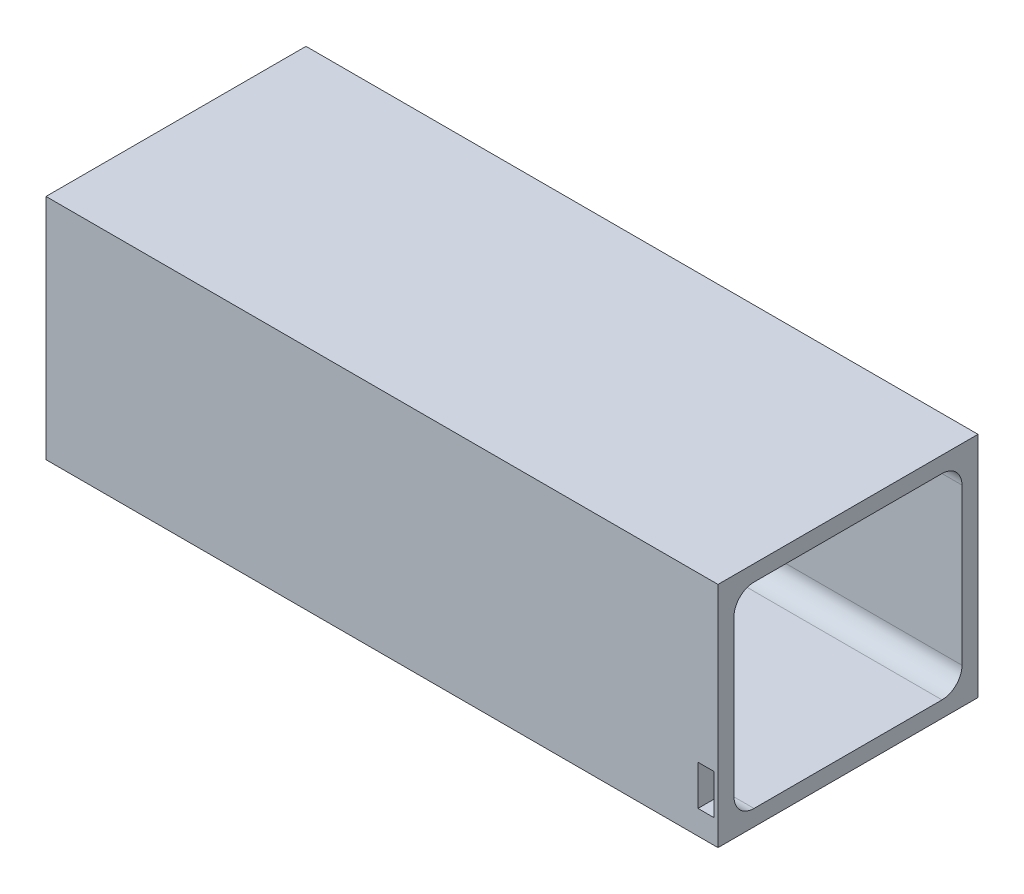
SolidWorks part; units mm, degrees
material "PET"
ref_plane "Спереди" through (0, 0, 0) normal (0, 0, 1) x (1, 0, 0)
ref_plane "Сверху" through (0, 0, 0) normal (0, 1, 0) x (1, 0, 0)
ref_plane "Справа" through (0, 0, 0) normal (1, 0, 0) x (0, 0, -1)
sketch "Эскиз1" plane through (0, 0, 0) normal (1, 0, 0) x (0, 0, -1)
  line L1 (23.5, -24.5) -> (-23.5, -24.5)
  line L2 (28.5, -19.5) -> (28.5, 19.5)
  line L3 (23.5, 24.5) -> (-23.5, 24.5)
  line L4 (-28.5, -19.5) -> (-28.5, 19.5)
  line L5 (28.5, -24.5) -> (-28.5, 24.5) construction
  line L6 (28.5, 24.5) -> (-28.5, -24.5) construction
  line L7 (32.5, -28.5) -> (-32.5, -28.5)
  line L8 (32.5, -28.5) -> (32.5, 28.5)
  line L9 (32.5, 28.5) -> (-32.5, 28.5)
  line L10 (-32.5, -28.5) -> (-32.5, 28.5)
  line L11 (32.5, -28.5) -> (-32.5, 28.5) construction
  line L12 (32.5, 28.5) -> (-32.5, -28.5) construction
  arc A0 (-23.5, -24.5) -> (-28.5, -19.5) centre (-23.5, -19.5) cw
  arc A1 (23.5, -24.5) -> (28.5, -19.5) centre (23.5, -19.5) ccw
  arc A2 (28.5, 19.5) -> (23.5, 24.5) centre (23.5, 19.5) ccw
  arc A3 (-23.5, 24.5) -> (-28.5, 19.5) centre (-23.5, 19.5) ccw
  point P0 (0, 0)
  point P5 (0, 0)
  dimension "D5" = 5
  dimension "D1" = 57
  dimension "D2" = 49
  dimension "D3" = 4
  dimension "D4" = 4
extrude "Бобышка-Вытянуть1" add sketch "Эскиз1" against normal blind 167
sketch "Эскиз2" plane through (0, 0, 32.5) normal (0, 0, 1) x (1, 0, 0)
  line L0 (0, 28.5) -> (0, -28.5) construction
  line L1 (-1, -22.5) -> (-5, -22.5)
  line L2 (-1, -22.5) -> (-1, -12.5)
  line L3 (-1, -12.5) -> (-5, -12.5)
  line L4 (-5, -22.5) -> (-5, -12.5)
  line L5 (-167, -28.5) -> (0, -28.5) construction
  dimension "D1" = 4
  dimension "D2" = 10
  dimension "D3" = 1
  dimension "D4" = 6
extrude "Вырез-Вытянуть1" cut sketch "Эскиз2" against normal blind 10
sketch "Эскиз3" plane through (-167, 0, 0) normal (-1, 0, 0) x (0, 0, 1)
  line L1 (32.5, -28.5) -> (-32.5, -28.5)
  line L2 (32.5, -28.5) -> (32.5, 28.5)
  line L3 (32.5, 28.5) -> (-32.5, 28.5)
  line L4 (-32.5, -28.5) -> (-32.5, 28.5)
  line L5 (32.5, -28.5) -> (-32.5, 28.5) construction
  line L6 (32.5, 28.5) -> (-32.5, -28.5) construction
  point P0 (0, 0)
extrude "Бобышка-Вытянуть2" add sketch "Эскиз3" along normal blind 1
